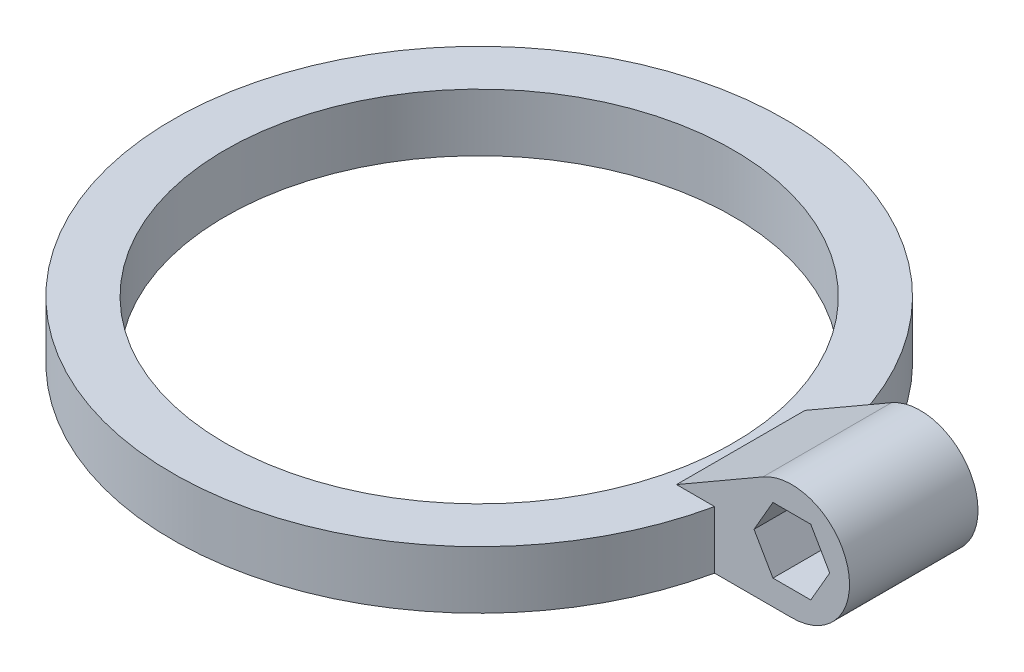
SolidWorks part; units mm, degrees
ref_plane "Front Plane" through (0, 0, 0) normal (0, 0, 1) x (1, 0, 0)
ref_plane "Top Plane" through (0, 0, 0) normal (0, 1, 0) x (1, 0, 0)
ref_plane "Right Plane" through (0, 0, 0) normal (1, 0, 0) x (0, 0, -1)
sketch "Sketch2" plane through (0, 0, 0) normal (0, 1, 0) x (1, 0, 0)
  line L0 (0, 0) -> (-21.2702, 0) construction
  line L2 (-11.7887, -9.8) -> (0, -9.8)
  line L3 (0, -9.8) -> (0, 9.8)
  line L4 (-11.7887, 9.8) -> (0, 9.8)
  line L5 (-21.2702, 0) -> (-57.5, 0) construction
  circle A1 centre (-57.5, 0) radius 38.75
  arc A2 (-11.7887, 9.8) -> (-11.7887, -9.8) centre (-57.5, 0) ccw
  dimension "D3" = 77.5
  dimension "D4" = 8
  dimension "D2" = 19.6
  dimension "D5" = 57.5
extrude "Boss-Extrude1" add sketch "Sketch2" against normal blind 8.8
sketch "Sketch3" plane through (0, 0, 0) normal (0, 0, 1) x (1, 0, 0)
  line L0 (0, -8.8) -> (0, 0)
  line L1 (0, 0) -> (-17.6, 0)
  line L2 (-17.6, 0) -> (-4.4, 7.621)
  arc A0 (0, -8.8) -> (-4.4, 7.621) centre (0, 0) ccw
  dimension "D1" = 8.8
  dimension "D2" = 30
extrude "Boss-Extrude2" add sketch "Sketch3" along normal blind 9.8 and the other way blind 9.8
sketch "Sketch4" plane through (0, 0, 0) normal (0, 0, 1) x (1, 0, 0)
  line L0 (0, 0) -> (5.7735, 0) construction
  line L1 (5.7735, 0) -> (2.8868, 5)
  line L2 (2.8868, 5) -> (-2.8868, 5)
  line L3 (-2.8868, 5) -> (-5.7735, 0)
  line L4 (-5.7735, 0) -> (-2.8868, -5)
  line L5 (-2.8868, -5) -> (2.8868, -5)
  line L6 (2.8868, -5) -> (5.7735, 0)
  circle A0 centre (0, 0) radius 5 construction
  dimension "D1" = 10
extrude "Cut-Extrude1" cut sketch "Sketch4" against normal up to next and the other way up to next
sketch "Sketch5" plane through (0, 0, 0) normal (0, 0, 1) x (1, 0, 0)
  line L0 (0, 0) -> (0, -5) construction
  line L1 (-1, -5) -> (1, -5)
  line L2 (1, -5) -> (1, -6)
  line L3 (1, -6) -> (-1, -6)
  line L4 (-1, -6) -> (-1, -5)
  point P7 (0, -5)
  dimension "D1" = 1
  dimension "D2" = 2
  dimension "D3" = 5
extrude "Cut-Extrude2" cut sketch "Sketch5" against normal up to next
